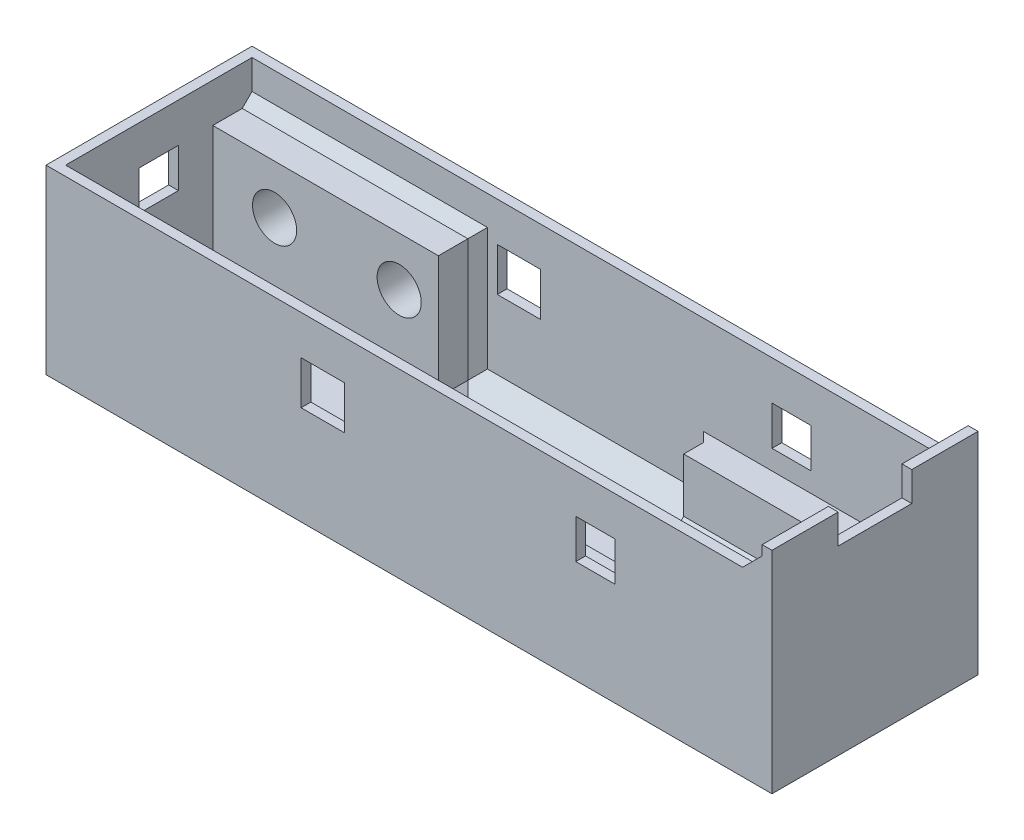
SolidWorks part; units mm, degrees
ref_plane "Płaszczyzna przednia" through (0, 0, 0) normal (0, 0, 1) x (1, 0, 0)
ref_plane "Płaszczyzna górna" through (0, 0, 0) normal (0, 1, 0) x (1, 0, 0)
ref_plane "Płaszczyzna prawa" through (0, 0, 0) normal (1, 0, 0) x (0, 0, -1)
sketch "Szkic1" plane through (0, 0, 0) normal (0, 1, 0) x (1, 0, 0)
  line L1 (-37, -10.5) -> (37, -10.5)
  line L2 (-37, -10.5) -> (-37, 10.5)
  line L3 (-37, 10.5) -> (37, 10.5)
  line L4 (37, -10.5) -> (37, 10.5)
  line L5 (-37, -10.5) -> (37, 10.5) construction
  line L6 (-37, 10.5) -> (37, -10.5) construction
  point P0 (0, 0)
  dimension "D1" = 21
  dimension "D2" = 74
extrude "Dodanie-wyciągnięcie1" add sketch "Szkic1" along normal blind 1
sketch "Szkic2" plane through (0, 1, 0) normal (0, 1, 0) x (1, 0, 0)
  line L0 (-37, 10.5) -> (-37, 9.5)
  line L1 (-37, 10.5) -> (-37, -10.5) construction
  line L2 (-36, 9.5) -> (36, 9.5)
  line L3 (36, 9.5) -> (36, -9.5)
  line L4 (36, -9.5) -> (-36, -9.5)
  line L5 (-37, -9.5) -> (-37, -10.5)
  line L6 (-37, -10.5) -> (37, -10.5) construction
  line L7 (-37, -10.5) -> (37, -10.5)
  line L8 (37, -10.5) -> (37, 10.5)
  line L9 (37, 10.5) -> (-37, 10.5)
  line L12 (-37, -9.5) -> (-37, 9.5)
  line L14 (-36, -9.5) -> (-36, 9.5)
  dimension "D1" = 1
  dimension "D2" = 1
  dimension "D3" = 1
extrude "Dodanie-wyciągnięcie2" add sketch "Szkic2" along normal blind 17.5
sketch "Szkic3" plane through (0, 1, 0) normal (0, 1, 0) x (1, 0, 0)
  line L0 (-4, -9.5) -> (-4, -6.5)
  line L1 (-4, -6.5) -> (36, -6.5)
  line L2 (36, 9.5) -> (36, -9.5) construction
  line L3 (36, -6.5) -> (36, -9.5)
  line L4 (36, -9.5) -> (-4, -9.5)
  line L5 (11, 9.5) -> (11, 6.5)
  line L6 (-36, 9.5) -> (36, 9.5) construction
  line L7 (11, 6.5) -> (36, 6.5)
  line L8 (36, 6.5) -> (36, 9.5)
  line L9 (36, 9.5) -> (11, 9.5)
  point P12 (0, 0)
  point P16 (0, 0)
  dimension "D1" = 3
  dimension "D2" = 25
  dimension "D3" = 40
extrude "Dodanie-wyciągnięcie3" add sketch "Szkic3" along normal offset from surface (7.5 mm away) 10 up to face at (0, 18.5, 0)
sketch "Szkic4" plane through (0, 18.5, 0) normal (0, 1, 0) x (1, 0, 0)
  line L0 (37, 10.5) -> (36, 10.5)
  line L1 (37, 10.5) -> (-37, 10.5) construction
  line L2 (36, 10.5) -> (36, 3.75)
  line L3 (36, 9.5) -> (36, -9.5) construction
  line L4 (36, 3.75) -> (37, 3.75)
  line L5 (37, -10.5) -> (37, 10.5) construction
  line L6 (37, 3.75) -> (37, 10.5)
  line L7 (36, -3.75) -> (36, -10.5)
  line L8 (-37, -10.5) -> (37, -10.5) construction
  line L9 (36, -10.5) -> (37, -10.5)
  line L10 (37, -10.5) -> (37, -3.75)
  line L11 (37, -3.75) -> (36, -3.75)
  point P15 (37, 0)
  dimension "D1" = 3.75
extrude "Dodanie-wyciągnięcie4" add sketch "Szkic4" along normal blind 3
chamfer "Sfazowanie1" distance 2 2 edges at (36, 18.5, -10) (36, 18.5, 10)
sketch "Szkic5" plane through (0, 0, -9.5) normal (0, 0, 1) x (1, 0, 0)
  line L0 (36, 20.5) -> (36, 8.5) construction
  line L1 (34, 18.5) -> (-37, 18.5) construction
  circle A0 centre (-17, 9.5) radius 2.25
  circle A1 centre (-29.7, 9.5) radius 2.25
  dimension "D4" = 4.5
  dimension "D1" = 53
  dimension "D2" = 12.7
  dimension "D3" = 9
extrude "Wytnij-wyciągnięcie1" cut sketch "Szkic5" against normal through all
sketch "Szkic11" plane through (0, 0, -9.5) normal (0, 0, 1) x (1, 0, 0)
  line L0 (-36, 18.5) -> (34, 18.5) construction
  line L1 (-36, 14.5) -> (-13, 14.5)
  line L2 (-36, 14.5) -> (-36, 1)
  line L3 (-36, 1) -> (-13, 1)
  line L4 (-13, 14.5) -> (-13, 1)
  circle A0 centre (-17, 9.5) radius 2.25 construction
  dimension "D1" = 4
  dimension "D2" = 4
extrude "Dodanie-wyciągnięcie8" add sketch "Szkic11" along normal blind 4
chamfer "Sfazowanie2" distance 2 angle 45 6 edges at (36, 8.5, 8) (36, 8.5, -8) (16, 1, 6.5) (36, 1, 0) (23.5, 1, -6.5) (-1, 1, -9.5)
sketch "Szkic8" plane through (0, 0, 0) normal (0, -1, 0) x (1, 0, 0)
  text T0 "oscyloskop-0v5" font "Century Gothic" height 6
  point P1 (-30.4271, 0.5099)
extrude "Wytnij-wyciągnięcie3" cut sketch "Szkic8" against normal blind 0.3
sketch "Szkic9" plane through (0, 8.5, 0) normal (0, 1, 0) x (1, 0, 0)
  line L0 (-4, -9.5) -> (34, -9.5) construction
  line L1 (-2.2903, -8.5) -> (-0.2903, -8.5)
  line L2 (-2.2903, -8.5) -> (-2.2903, -9.5)
  line L3 (-2.2903, -9.5) -> (-0.2903, -9.5)
  line L4 (-0.2903, -8.5) -> (-0.2903, -9.5)
  dimension "D1" = 2
  dimension "D2" = 1
extrude "Dodanie-wyciągnięcie6" [suppressed] add sketch "Szkic9" along normal blind 4
chamfer "Sfazowanie3" [suppressed] distance 1 angle 45
chamfer "Sfazowanie4" [suppressed] distance 1 angle 45
extrude "Wytnij-wyciągnięcie8" cut sketch "Szkic5<2>" along normal up to surface (19 mm away) up to face at (7.5, 10.875, 9.5)
sketch "Szkic5<2>" plane through (0, 0, -9.5) normal (0, 0, 1) x (1, 0, 0) same geometry as "Szkic5"
chamfer "Sfazowanie5" distance 1 angle 45 6 edges at (11, 5.75, -9.5) (11, 1, -6) (-24.5, 14.5, -9.5) (-13, 8.75, -9.5) (-13, 1, -6.5) (-24.5, 1, -5.5)
sketch "Szkic7" plane through (0, 0, 10.5) normal (0, 0, 1) x (1, 0, 0)
  line L0 (-37, 18.5) -> (34, 18.5) construction
  line L1 (17, 14.5) -> (21, 14.5)
  line L2 (17, 14.5) -> (17, 10.5)
  line L3 (17, 10.5) -> (21, 10.5)
  line L4 (21, 14.5) -> (21, 10.5)
  line L5 (37, 21.5) -> (37, 0) construction
  line L6 (-37, 18.5) -> (-37, 0) construction
  line L7 (-6.5816, 14.5) -> (-11, 14.5)
  line L8 (-6.5816, 14.5) -> (-6.5816, 10.0816)
  line L9 (-6.5816, 10.0816) -> (-11, 10.0816)
  line L10 (-11, 14.5) -> (-11, 10.0816)
  dimension "D1" = 4
  dimension "D2" = 16
  dimension "D3" = 4
  dimension "D4" = 26
extrude "Wytnij-wyciągnięcie2" cut sketch "Szkic7" against normal through all
sketch "Szkic12" plane through (-37, 0, 0) normal (-1, 0, 0) x (0, 0, 1)
  line L0 (-10.5, 18.5) -> (10.5, 18.5) construction
  line L1 (-2, 10.5) -> (2, 10.5)
  line L2 (-2, 10.5) -> (-2, 14.5)
  line L3 (-2, 14.5) -> (2, 14.5)
  line L4 (2, 10.5) -> (2, 14.5)
  line L5 (-2, 10.5) -> (2, 14.5) construction
  line L6 (-2, 14.5) -> (2, 10.5) construction
  line L7 (-10.5, 0) -> (10.5, 0) construction
  point P0 (0, 12.5)
  point P7 (0, 0)
  point P10 (0, 0)
  dimension "D1" = 4
  dimension "D2" = 4
extrude "Wytnij-wyciągnięcie9" cut sketch "Szkic12" against normal up to next
